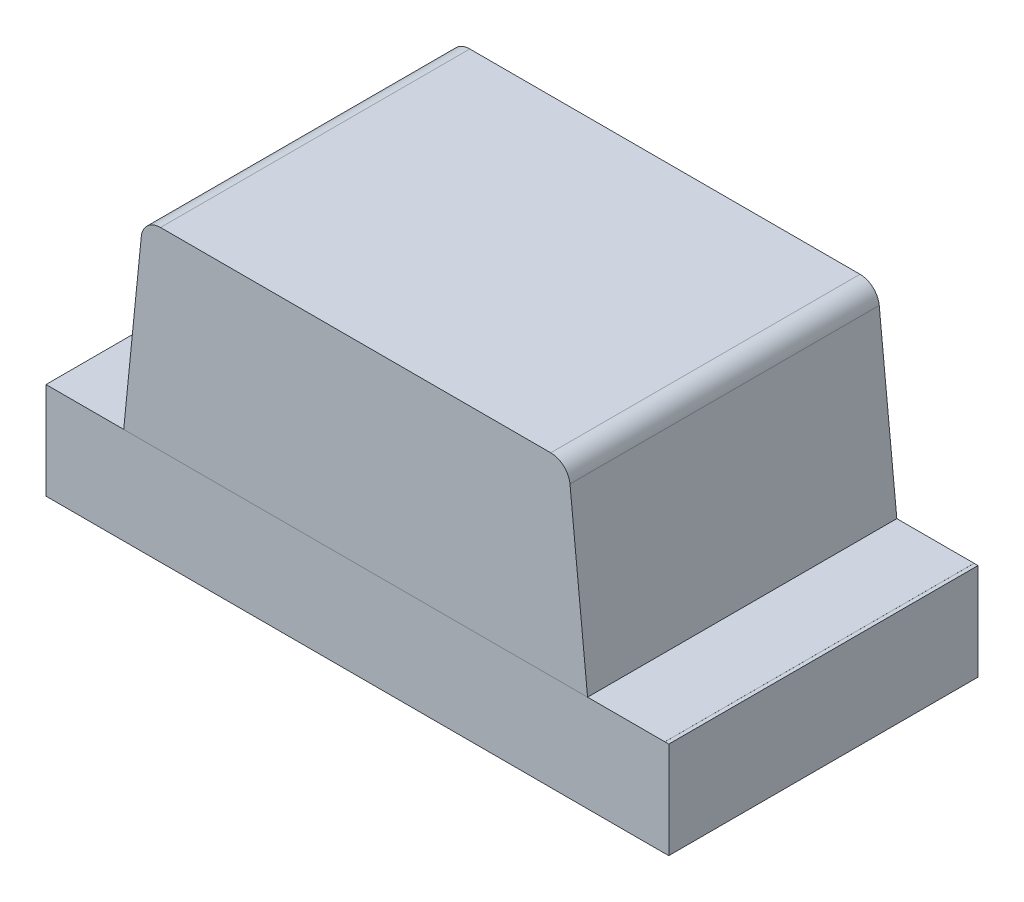
SolidWorks part; units mm, degrees
note: The reader was unsure of these and kept them because the rebuilt part matched: shared geometry of "Sketch1<3>", "Sketch2<3>".
ref_plane "Front Plane" through (0, 0, 0) normal (0, 0, 1) x (1, 0, 0)
ref_plane "Top Plane" through (0, 0, 0) normal (0, 1, 0) x (1, 0, 0)
ref_plane "Right Plane" through (0, 0, 0) normal (1, 0, 0) x (0, 0, -1)
sketch "Sketch1" plane through (0, 0, 0) normal (0, 0, 1) x (1, 0, 0)
  line L0 (-0.8, 0.125) -> (0.8, -0.125) construction
  line L1 (-0.8, 0.125) -> (0.8, 0.125)
  line L2 (-0.8, 0.125) -> (-0.8, -0.125)
  line L3 (-0.8, -0.125) -> (0.8, -0.125)
  line L4 (0.8, 0.125) -> (0.8, -0.125)
  line L5 (-0.55, 0.625) -> (-0.6, 0.125)
  line L6 (-0.6, 0.125) -> (0.6, 0.125)
  line L7 (0.6, 0.125) -> (0.55, 0.625)
  line L8 (0.55, 0.625) -> (-0.55, 0.625)
  line L9 (0, 0.625) -> (0, 0.125) construction
  dimension "D1" = 0.25
  dimension "D2" = 1.6
  dimension "D3" = 1.2
  dimension "D4" = 1.1
  dimension "D5" = 0.75
extrude "Extrude1" add sketch "Sketch1" along normal mid plane 0.8 contours L4 L1 L2 L3
extrude "Extrude2" add sketch "Sketch1<3>" along normal mid plane 0.8 separate body contours L7 L8 L5 L1
sketch "Sketch1<3>" plane through (0, 0, 0) normal (0, 0, 1) x (1, 0, 0) same geometry as "Sketch1"
sketch "Sketch2" plane through (0, -0.125, 0) normal (0, -1, 0) x (1, 0, 0)
  line L0 (-0.8, -0.4) -> (0.8, -0.4) construction
  line L1 (-0.8, 0.4) -> (-0.5, 0.4)
  line L2 (-0.8, 0.4) -> (-0.8, -0.4)
  line L3 (-0.8, -0.4) -> (-0.5, -0.4)
  line L4 (-0.5, 0.4) -> (-0.5, -0.4)
  line L5 (0, 0) -> (0, 0.4) construction
  line L6 (-0.8, 0.4) -> (0.8, 0.4) construction
  line L7 (0.5, 0.4) -> (0.5, -0.4)
  line L8 (0.8, -0.4) -> (0.5, -0.4)
  line L9 (0.8, 0.4) -> (0.8, -0.4)
  line L10 (0.8, 0.4) -> (0.5, 0.4)
  line L11 (-0.3398, 0.4) -> (-0.3398, -0.4)
  line L12 (-0.3398, -0.4) -> (0.3253, 0)
  line L13 (0.55, 0) -> (-0.55, 0) construction
  line L14 (0.3253, 0) -> (-0.3398, 0.4)
  line M1 (-0.8, -0.4) -> (0.8, -0.4)
  line M2 (0.8, -0.4) -> (0.8, 0.4)
  line M3 (0.8, 0.4) -> (-0.8, 0.4)
  line M4 (-0.8, 0.4) -> (-0.8, -0.4)
  dimension "D1" = 0.3
sketch "Sketch3" plane through (0, 0.125, 0) normal (0, 1, 0) x (-1, 0, 0)
  line L0 (-0.8, 0.4) -> (-0.5, 0.4) construction
  line L1 (0.8, -0.4) -> (0.6, -0.4)
  line L2 (0.8, -0.4) -> (0.8, 0.4)
  line L3 (0.8, 0.4) -> (0.6, 0.4)
  line L4 (0.6, -0.4) -> (0.6, 0.4)
  line L5 (-0.8, -0.4) -> (-0.6, -0.4)
  line L6 (-0.8, -0.4) -> (-0.8, 0.4)
  line L7 (-0.8, 0.4) -> (-0.6, 0.4)
  line L8 (-0.6, -0.4) -> (-0.6, 0.4)
  line L9 (-0.6, 0.4) -> (-0.6, -0.4) construction
  line M1 (-0.8, -0.4) -> (0.8, -0.4)
  line M2 (0.8, -0.4) -> (0.8, 0.4)
  line M3 (0.8, 0.4) -> (-0.8, 0.4)
  line M4 (-0.8, 0.4) -> (-0.8, -0.4)
extrude "Extrude3" add sketch "Sketch2" against normal blind 0.01 and the other way blind 0.0001 separate body
extrude "Extrude4" add sketch "Sketch2<3>" against normal blind 0.01 and the other way blind 0.0001 separate body contours L4 M3 M4 M1 | L7 M3 M1 M2
sketch "Sketch2<3>" plane through (0, -0.125, 0) normal (0, -1, 0) x (1, 0, 0) same geometry as "Sketch2"
extrude "Extrude5" add sketch "Sketch3" against normal blind 0.01 and the other way blind 0.0001 separate body contours L4 M1 M2 M3 | L8 M1 M3 M4
fillet "Fillet1" radius 0.05 2 edges at (0.55, 0.625, 0) (-0.55, 0.625, 0)
sketch "Sketch5" plane through (0.8, 0, 0) normal (1, 0, 0) x (0, 0, -1)
  line L1 (-0.4, 0.125) -> (0.4, 0.125)
  line L2 (-0.4, 0.125) -> (-0.4, -0.125)
  line L3 (-0.4, -0.125) -> (0.4, -0.125)
  line L4 (0.4, 0.125) -> (0.4, -0.125)
extrude "Extrude6" add sketch "Sketch5" along normal blind 0.01 and the other way blind 0.0001
sketch "Sketch6" plane through (-0.8, 0, 0) normal (-1, 0, 0) x (0, 0, 1)
  line L1 (-0.4, 0.1251) -> (0.4, 0.1251)
  line L2 (-0.4, 0.1251) -> (-0.4, -0.1251)
  line L3 (-0.4, -0.1251) -> (0.4, -0.1251)
  line L4 (0.4, 0.1251) -> (0.4, -0.1251)
extrude "Extrude7" add sketch "Sketch6" against normal blind 0.01 and the other way blind 0.001
sketch "Sketch7" plane through (0, -0.1251, 0) normal (0, -1, 0) x (1, 0, 0)
  line L0 (-0.7443, 0.4) -> (-0.7443, -0.4) construction
  line L1 (-0.801, 0.4) -> (-0.5, 0.4) construction
  line L2 (-0.801, -0.4) -> (-0.5, -0.4) construction
  text T0 "www.SunLED.com" font "Verdana" height 0.05
extrude "Cut-Extrude1" cut sketch "Sketch7" against normal blind 0.01
